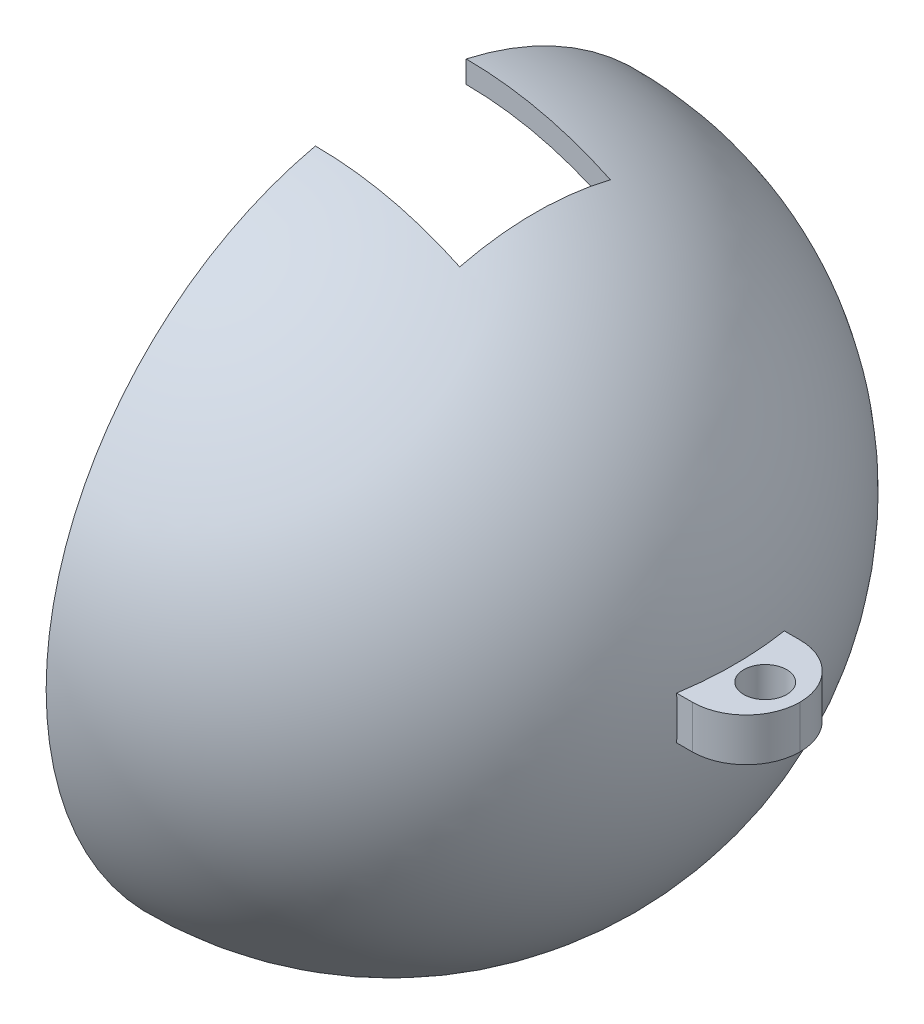
SolidWorks part; units mm, degrees
ref_plane "前视基准面" through (0, 0, 0) normal (0, 0, 1) x (1, 0, 0)
ref_plane "上视基准面" through (0, 0, 0) normal (0, 1, 0) x (1, 0, 0)
ref_plane "右视基准面" through (0, 0, 0) normal (1, 0, 0) x (0, 0, -1)
sketch "草图1" plane through (0, 0, 0) normal (1, 0, 0) x (0, 0, -1)
  line L0 (-16, 0) -> (-15, 0)
  line L1 (15, 0) -> (16, 0)
  arc A0 (15, 0) -> (-15, 0) centre (0, 0) ccw
  arc A1 (16, 0) -> (-16, 0) centre (0, 0) ccw
  point P6 (0, 0)
  point P7 (15, 0)
  point P8 (-15, 0)
  dimension "D1" = 30
  dimension "D2" = 32
revolve "旋转2" add sketch "草图1" angle 180 about L1
ref_plane "基准面7" through (15, 0, 0) normal (1, 0, 0) x (0, 0, -1)
sketch "草图2" plane through (15, 0, 0) normal (1, 0, 0) x (0, 0, -1)
  line L1 (-2.5, -1) -> (2.5, -1)
  line L2 (-2.5, -1) -> (-2.5, 1)
  line L3 (-2.5, 1) -> (2.5, 1)
  line L4 (2.5, -1) -> (2.5, 1)
  line L5 (-2.5, -1) -> (2.5, 1) construction
  line L6 (-2.5, 1) -> (2.5, -1) construction
  point P0 (0, 0)
  dimension "D1" = 2
  dimension "D2" = 5
extrude "凸台-拉伸1" add sketch "草图2" along normal blind 4
sketch "草图3" plane through (0, 1, 0) normal (0, 1, 0) x (1, 0, 0)
  line L2 (17.3859, 2.5) -> (17.3859, -2.5)
  line L3 (19, -2.5) -> (15.7718, -2.5) construction
  line L4 (19, 2.5) -> (15.7718, 2.5) construction
  circle A0 centre (17.3859, 0) radius 1
  point P2 (0, 0)
  point P3 (17.3859, 0)
  point P10 (0, 0)
  point P11 (0, 0)
  dimension "D1" = 2
extrude "切除-拉伸1" cut sketch "草图3" against normal blind 5 contours A0
fillet "圆角1" radius 2.5 1 edges at (19, 0, -2.5)
fillet "圆角2" radius 2.5 1 edges at (19, 0, 2.5)
ref_plane "基准面8" through (0, 18.6269, 0) normal (0, 1, 0) x (1, 0, 0)
sketch "草图4" plane through (0, 18.6269, 0) normal (0, 1, 0) x (1, 0, 0)
  line L0 (0, 15) -> (0, -15) construction
  line L1 (0, 3.5) -> (6.7, 3.5)
  line L2 (0, 3.5) -> (0, -3.5)
  line L3 (0, -3.5) -> (6.7, -3.5)
  line L4 (6.7, 3.5) -> (6.7, -3.5)
  dimension "D1" = 7
  dimension "D2" = 6.7
extrude "切除-拉伸2" cut sketch "草图4" against normal blind 15
